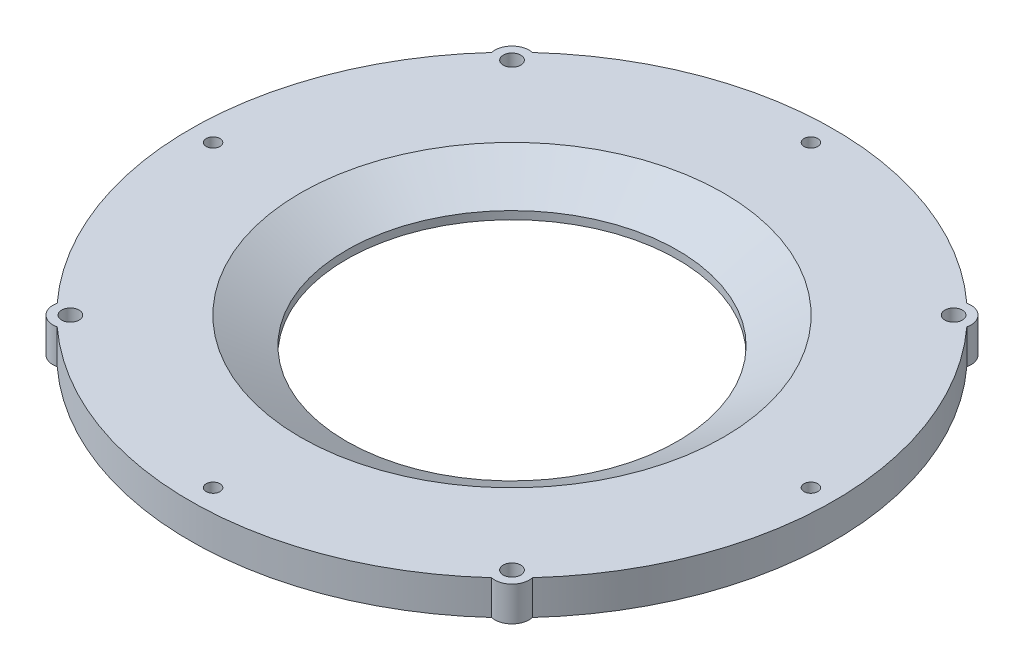
SolidWorks part; units mm, degrees
material "6061-T6 (SS)"
ref_plane "Front Plane" through (0, 0, 0) normal (0, 0, 1) x (1, 0, 0)
ref_plane "Top Plane" through (0, 0, 0) normal (0, 1, 0) x (1, 0, 0)
ref_plane "Right Plane" through (0, 0, 0) normal (1, 0, 0) x (0, 0, -1)
sketch "Sketch1" plane through (0, 0, 0) normal (0, 1, 0) x (1, 0, 0)
  line L0 (0, 88.9) -> (0, -88.9) construction
  line L1 (-88.9, 0) -> (88.9, 0) construction
  line L2 (-60.9759, -60.9759) -> (60.9759, 60.9759) construction
  line L3 (60.9759, -60.9759) -> (-60.9759, 60.9759) construction
  arc A0 (-65.6301, 59.9658) -> (-65.6301, -59.9658) centre (0, 0) ccw
  arc A1 (-59.9658, 65.6301) -> (-65.6301, 59.9658) centre (-60.9759, 60.9759) ccw
  arc A2 (65.6301, 59.9658) -> (59.9658, 65.6301) centre (60.9759, 60.9759) ccw
  arc A3 (59.9658, -65.6301) -> (65.6301, -59.9658) centre (60.9759, -60.9759) ccw
  arc A4 (-65.6301, -59.9658) -> (-59.9658, -65.6301) centre (-60.9759, -60.9759) ccw
  arc A5 (59.9658, 65.6301) -> (-59.9658, 65.6301) centre (0, 0) ccw
  arc A6 (65.6301, -59.9658) -> (65.6301, 59.9658) centre (0, 0) ccw
  arc A7 (-59.9658, -65.6301) -> (59.9658, -65.6301) centre (0, 0) ccw
  circle A8 centre (-60.9759, 60.9759) radius 2.413
  circle A9 centre (60.9759, 60.9759) radius 2.413
  circle A10 centre (60.9759, -60.9759) radius 2.413
  circle A11 centre (-60.9759, -60.9759) radius 2.413
  circle A12 centre (0, 0) radius 83.82 construction
  point P10 (0, 0)
  point P13 (0, 0)
  dimension "D1" = 177.8
  dimension "D3" = 9.525
  dimension "D4" = 4.826
  dimension "D7" = 167.64
  dimension "D2" = 90
  dimension "D5" = 45
  dimension "D6" = 172.466
extrude "Boss-Extrude1" add sketch "Sketch1" along normal blind 9.525
sketch "Sketch2" plane through (0, 9.525, 0) normal (0, 1, 0) x (1, 0, 0)
  circle A0 centre (0, 0) radius 45.72
extrude "Cut-Extrude1" cut sketch "Sketch2" against normal blind 12.7
sketch "Sketch4" plane through (0, 9.525, 0) normal (0, 1, 0) x (1, 0, 0)
  line L0 (0, 0) -> (0, 115.2639) construction
  circle A0 centre (0, 82.55) radius 1.905
  dimension "D1" = 3.81
  dimension "D2" = 82.55
extrude "Cut-Extrude3" cut sketch "Sketch4" against normal blind 12.7
pattern_circular "CirPattern2" count 4 over 360 about axis through (0, 9.525, 0) along (0, 1, 0) of "Cut-Extrude3"
ref_plane "Plane3" through (-62.8618, 0, -62.8618) normal (-0.7071, 0, -0.7071) x (0, -1, 0)
sketch "Sketch10" plane through (-62.8618, 0, -62.8618) normal (-0.7071, 0, -0.7071) x (0, -1, 0)
  line L0 (0, 0) -> (-9.652, 0) construction
  circle A1 centre (-4.826, 0) radius 0.6985
  dimension "D2" = 1.397
  dimension "D1" = 9.652
extrude "Cut-Extrude5" cut sketch "Sketch10" against normal blind 3.175
pattern_circular "CirPattern5" count 4 over 360 about axis through (0, 9.525, 0) along (0, 1, 0) of "Cut-Extrude5"
chamfer "Chamfer1" distance 12.7 angle 30 1 edges at (0, 9.525, 45.72) first distance on face at (-80.645, 9.525, 0)
